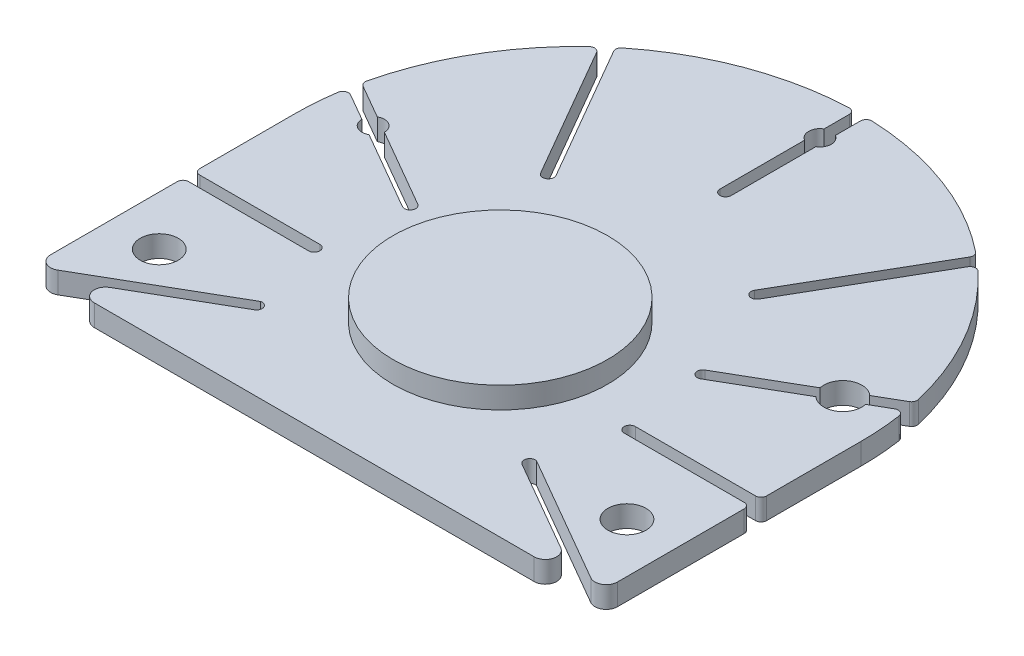
SolidWorks part; units mm, degrees
material "ABS"
ref_plane "Front" through (0, 0, 0) normal (0, 0, 1) x (1, 0, 0)
ref_plane "Top" through (0, 0, 0) normal (0, 1, 0) x (1, 0, 0)
ref_plane "Right" through (0, 0, 0) normal (1, 0, 0) x (0, 0, -1)
ref_axis "Axis1" through (0, 0, 55) along (0, 0, -1)
sketch "Sketch2" plane through (0, 0, 0) normal (0, 1, 0) x (1, 0, 0)
  line L0 (40.7247, 1.878) -> (26.4808, -6.3457)
  line L1 (25.4808, -4.6137) -> (39.7247, 3.6101)
  line L2 (42.7247, 5.3421) -> (48.4844, 8.6675)
  line L3 (32.9512, 34.5935) -> (19.366, 11.0632)
  line L4 (17.634, 12.0632) -> (31.6058, 36.2632)
  line L5 (1, 47.4797) -> (1, 43.0109)
  line L6 (1, 39.5468) -> (1, 24.5203)
  line L7 (-1, 24.5203) -> (-1, 39.5468)
  line L8 (-1, 43.0109) -> (-1, 47.4797)
  line L9 (-31.6058, 36.2632) -> (-17.634, 12.0632)
  line L10 (-19.366, 11.0632) -> (-32.9512, 34.5935)
  line L11 (-48.4844, 8.6675) -> (-42.5, 5.2124)
  line L12 (-39.5, 3.4803) -> (-25.4808, -4.6137)
  line L13 (-26.4808, -6.3457) -> (-40.5, 1.7483)
  line L14 (-43.5, 3.4803) -> (-48.2784, 6.2391)
  line L15 (-50.3, -1.7797) -> (-50.3, -18.4797)
  line L16 (-49.3, -19.4797) -> (-28, -19.4797)
  line L17 (-28, -21.4797) -> (-49.3, -21.4797)
  line L18 (-50.3, -22.4797) -> (-50.3, -44.9548)
  line L19 (-47.3, -46.6869) -> (-24.4658, -33.5036)
  line L20 (-23.7487, -35.3457) -> (-40.0333, -44.7477)
  line L21 (-39.0333, -48.4797) -> (39.0333, -48.4797)
  line L22 (40.0333, -44.7477) -> (23.7487, -35.3457)
  line L23 (24.4658, -33.5036) -> (47.3, -46.6869)
  line L24 (50.3, -44.9548) -> (50.3, -22.4797)
  line L25 (49.3, -21.4797) -> (28, -21.4797)
  line L26 (28, -19.4797) -> (49.3, -19.4797)
  line L27 (50.3, -18.4797) -> (50.3, -1.7797)
  line L28 (48.2784, 6.2391) -> (43.7247, 3.6101)
  circle A0 centre (-41.5, -34.4797) radius 2
  circle A1 centre (41.5, -34.4797) radius 2
  arc A2 (40.7247, 1.878) -> (43.7247, 3.6101) centre (41.7247, 3.6101) ccw
  arc A3 (25.4808, -4.6137) -> (26.4808, -6.3457) centre (25.9808, -5.4797) ccw
  arc A4 (42.7247, 5.3421) -> (39.7247, 3.6101) centre (41.7247, 3.6101) ccw
  arc A5 (48.4844, 8.6675) -> (48.9577, 9.763) centre (47.9844, 9.5335) ccw
  arc A6 (48.9577, 9.763) -> (34.5032, 34.8211) centre (0, -1.7797) ccw
  arc A7 (34.5032, 34.8211) -> (32.9512, 34.5935) centre (33.8172, 34.0935) ccw
  arc A8 (17.634, 12.0632) -> (19.366, 11.0632) centre (18.5, 11.5632) ccw
  arc A9 (31.6058, 36.2632) -> (31.3633, 37.545) centre (30.7398, 36.7632) ccw
  arc A10 (31.3633, 37.545) -> (2.0406, 48.4789) centre (0, -1.7797) ccw
  arc A11 (2.0406, 48.4789) -> (1, 47.4797) centre (2, 47.4797) ccw
  arc A12 (1, 39.5468) -> (1, 43.0109) centre (0, 41.2789) ccw
  arc A13 (-1, 24.5203) -> (1, 24.5203) centre (0, 24.5203) ccw
  arc A14 (-1, 43.0109) -> (-1, 39.5468) centre (0, 41.2789) ccw
  arc A15 (-1, 47.4797) -> (-2.0406, 48.4789) centre (-2, 47.4797) ccw
  arc A16 (-2.0406, 48.4789) -> (-31.3633, 37.545) centre (0, -1.7797) ccw
  arc A17 (-31.3633, 37.545) -> (-31.6058, 36.2632) centre (-30.7398, 36.7632) ccw
  arc A18 (-19.366, 11.0632) -> (-17.634, 12.0632) centre (-18.5, 11.5632) ccw
  arc A19 (-32.9512, 34.5935) -> (-34.5032, 34.8211) centre (-33.8172, 34.0935) ccw
  arc A20 (-34.5032, 34.8211) -> (-48.9577, 9.763) centre (0, -1.7797) ccw
  arc A21 (-48.9577, 9.763) -> (-48.4844, 8.6675) centre (-47.9844, 9.5335) ccw
  arc A22 (-39.5, 3.4803) -> (-42.5, 5.2124) centre (-41.5, 3.4803) ccw
  arc A23 (-26.4808, -6.3457) -> (-25.4808, -4.6137) centre (-25.9808, -5.4797) ccw
  arc A24 (-43.5, 3.4803) -> (-40.5, 1.7483) centre (-41.5, 3.4803) ccw
  arc A25 (-48.2784, 6.2391) -> (-49.7678, 5.5182) centre (-48.7784, 5.3731) ccw
  arc A26 (-49.7678, 5.5182) -> (-50.3, -1.7797) centre (0, -1.7797) ccw
  arc A27 (-50.3, -18.4797) -> (-49.3, -19.4797) centre (-49.3, -18.4797) ccw
  arc A28 (-28, -21.4797) -> (-28, -19.4797) centre (-28, -20.4797) ccw
  arc A29 (-49.3, -21.4797) -> (-50.3, -22.4797) centre (-49.3, -22.4797) ccw
  arc A30 (-50.3, -44.9548) -> (-47.3, -46.6869) centre (-48.3, -44.9548) ccw
  arc A31 (-23.7487, -35.3457) -> (-24.4658, -33.5036) centre (-24.2487, -34.4797) ccw
  arc A32 (-40.0333, -44.7477) -> (-39.0333, -48.4797) centre (-39.0333, -46.4797) ccw
  arc A33 (39.0333, -48.4797) -> (40.0333, -44.7477) centre (39.0333, -46.4797) ccw
  arc A34 (24.4658, -33.5036) -> (23.7487, -35.3457) centre (24.2487, -34.4797) ccw
  arc A35 (47.3, -46.6869) -> (50.3, -44.9548) centre (48.3, -44.9548) ccw
  arc A36 (50.3, -22.4797) -> (49.3, -21.4797) centre (49.3, -22.4797) ccw
  arc A37 (28, -19.4797) -> (28, -21.4797) centre (28, -20.4797) ccw
  arc A38 (49.3, -19.4797) -> (50.3, -18.4797) centre (49.3, -18.4797) ccw
  arc A39 (50.3, -1.7797) -> (49.7678, 5.5182) centre (0, -1.7797) ccw
  arc A40 (49.7678, 5.5182) -> (48.2784, 6.2391) centre (48.7784, 5.3731) ccw
  dimension "D1" = 17.634
  dimension "D2" = 18.5
  dimension "D3" = 23.7487
  dimension "D4" = 24.2487
  dimension "D5" = 24.4658
  dimension "D6" = 30.7398
  dimension "D7" = 31.3633
  dimension "D8" = 39.0333
  dimension "D9" = 41.5
  dimension "D10" = 1.7483
  dimension "D11" = 1.878
  dimension "D25" = 24.5203
extrude "Boss-Extrude1" add sketch "Sketch2" along normal blind 3.81
sketch "Sketch3" plane through (0, 3.81, 0) normal (0, 1, 0) x (1, 0, 0)
  line L0 (0, 41.2789) -> (0, -48.4797) construction
  line L1 (-39.0333, -48.4797) -> (39.0333, -48.4797) construction
  circle A0 centre (0, -15.4597) radius 19.05
  dimension "D2" = 38.1
  dimension "D1" = 33.02
extrude "Boss-Extrude2" add sketch "Sketch3" along normal blind 3.81
hole_wizard "1/4 Clearance Hole1" positions "Sketch4" profile "Sketch5" hole size "1/4" standard "ANSI Inch" end condition up to next
sketch "Sketch4" plane through (0, 3.81, 0) normal (0, 1, 0) x (1, 0, 0)
  point P0 (41.5, -34.4797)
  point P3 (41.7247, 3.6101)
  point P6 (-41.5, -34.4797)
sketch "Sketch5" plane through (41.5, 3.81, 34.4797) normal (1, 0, 0) x (0, 0, 1)
  line L0 (0, 0) -> (0, 3.81)
  line L1 (0, 3.81) -> (3.3782, 3.81)
  line L2 (3.3782, 3.81) -> (3.3782, 0)
  line L5 (3.3782, 0) -> (0, 0)
  line L11 (0, -6.35) -> (0, 107.95) construction
  dimension "Thru Hole Dia." = 6.7564
  dimension "Thru Hole Depth" = 3.81
